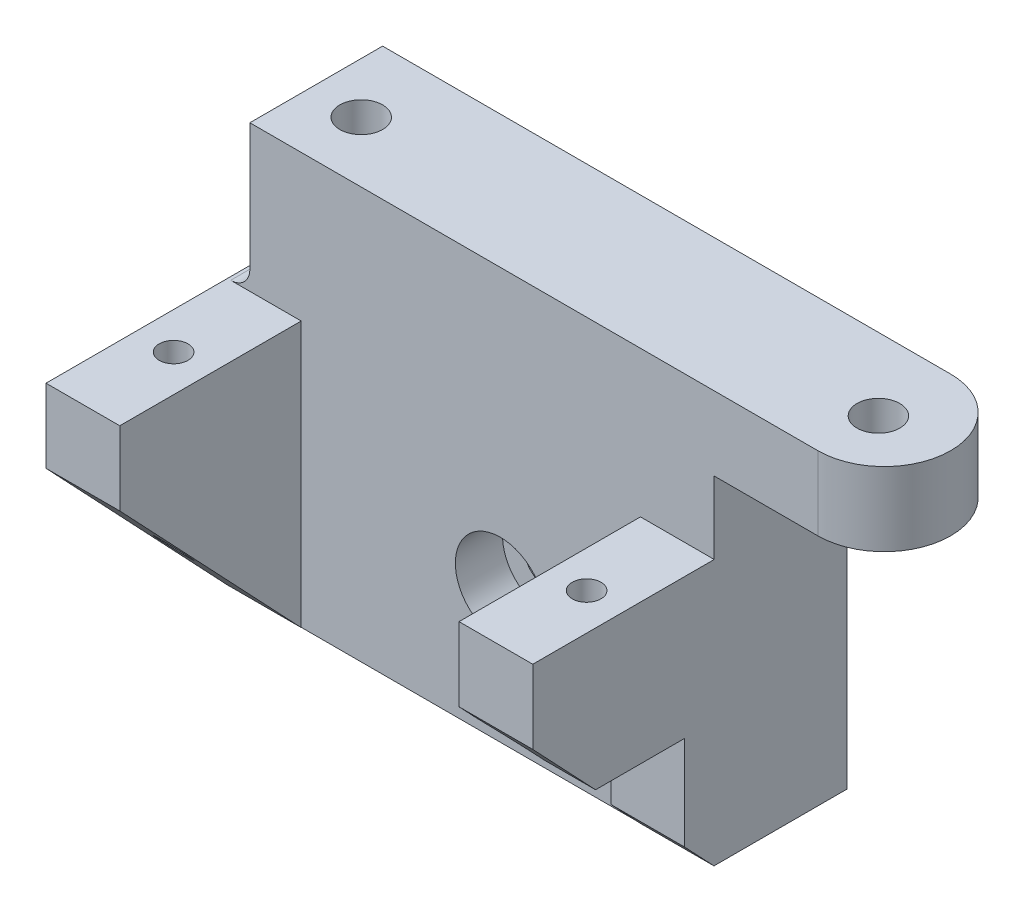
SolidWorks part; units mm, degrees
ref_plane "Front Plane" through (0, 0, 0) normal (0, 0, 1) x (1, 0, 0)
ref_plane "Top Plane" through (0, 0, 0) normal (0, 1, 0) x (1, 0, 0)
ref_plane "Right Plane" through (0, 0, 0) normal (1, 0, 0) x (0, 0, -1)
ref_plane "Model center" through (6, 0, 0) normal (1, 0, 0) x (0, 0, -1)
sketch "Sketch1" plane through (0, 0, 0) normal (0, 0, 1) x (1, 0, 0)
  line L0 (-4, 0) -> (4, 0)
  line L1 (-16.5, -8.9917) -> (16.5, -8.9917)
  line L2 (-16.5, -8.9917) -> (-16.5, 8.9917)
  line L3 (-16.5, 8.9917) -> (16.5, 8.9917)
  line L4 (16.5, -8.9917) -> (16.5, 8.9917)
  line L5 (-16.5, -8.9917) -> (16.5, 8.9917) construction
  line L6 (-16.5, 8.9917) -> (16.5, -8.9917) construction
  point P0 (0, 0)
  point P9 (0, 0)
  dimension "D1" = 8
  dimension "D2" = 33
extrude "Boss-Extrude1" add sketch "Sketch1" along normal blind 9 contours L1 L4 L3 L2 region at (-16.1242, 0, 0)
ref_plane "Plane1" through (0, 8.9917, 0) normal (0, 1, 0) x (1, 0, 0)
sketch "Sketch4" plane through (0, 8.9917, 0) normal (0, 1, 0) x (1, 0, 0)
  line L1 (0, 0) -> (0, -9) construction
  line L2 (-16.5, -9) -> (-11.5, -9)
  line L3 (-16.5, -9) -> (-16.5, -21.3)
  line L4 (-16.5, -21.3) -> (-11.5, -21.3)
  line L5 (-11.5, -9) -> (-11.5, -21.3)
  line L6 (-16.5, 0) -> (16.5, 0) construction
  line L7 (-16.5, -9) -> (16.5, -9) construction
  line L8 (11.5, -9) -> (11.5, -21.3)
  line L9 (16.5, -21.3) -> (11.5, -21.3)
  line L10 (16.5, -9) -> (16.5, -21.3)
  line L11 (16.5, -9) -> (11.5, -9)
  dimension "D1" = 5
  dimension "D2" = 12.3
extrude "Boss-Extrude2" add sketch "Sketch4" against normal blind 5
chamfer "Chamfer1" distance 12.3 distance2 13 2 edges at (-14, 3.9917, 9) (14, 3.9917, 9) first distance on face at (-14, 3.9917, 15.15) first distance on face at (14, 3.9917, 15.15)
sketch "Sketch2" plane through (0, 0, 0) normal (0, 0, -1) x (-1, 0, 0)
  line L0 (-10, 0) -> (-2, 0) construction
  circle A0 centre (-2, 0) radius 1.575
  circle A1 centre (-10, 0) radius 1.575
  point P12 (-6, 0)
  dimension "D2" = 3.15
  dimension "D1" = 8
  dimension "D3" = 6
extrude "Cut-Extrude1" cut sketch "Sketch2" against normal through all
sketch "Sketch3" plane through (0, 0, 9) normal (0, 0, 1) x (1, 0, 0)
  circle A0 centre (2, 0) radius 3.05
  circle A1 centre (10, 0) radius 3.05
  dimension "D1" = 6.1
extrude "Cut-Extrude2" cut sketch "Sketch3" against normal blind 3.2 and the other way through all
sketch "Sketch5" plane through (0, 8.9917, 0) normal (0, 1, 0) x (1, 0, 0)
  line L0 (0, 0) -> (0, -18.0516) construction
  line L1 (-16.5, 0) -> (16.5, 0) construction
  line L2 (-11.5, -15.15) -> (-16.5, -15.15) construction
  line L3 (-11.5, -21.3) -> (-11.5, -9) construction
  line L4 (-16.5, -21.3) -> (-16.5, 0) construction
  circle A0 centre (-14, -15.15) radius 0.975
  circle A1 centre (14, -15.15) radius 0.975
  dimension "D1" = 1.95
extrude "Cut-Extrude3" cut sketch "Sketch5" against normal up to surface (11.5 mm away) up to face at (-14, -2.5, 15.1579)
sketch "Sketch6" plane through (0, 8.9917, 0) normal (0, 1, 0) x (1, 0, 0)
  line L0 (-11.5, -9) -> (11.5, -9) construction
  line L1 (-16.5, -9) -> (16.5, -9)
  line L2 (-16.5, -9) -> (-16.5, 0)
  line L3 (-16.5, 0) -> (16.5, 0)
  line L4 (16.5, -9) -> (16.5, 0)
  line L5 (-16.5, -9) -> (16.5, 0) construction
  line L6 (-16.5, 0) -> (16.5, -9) construction
  point P0 (0, -4.5)
extrude "Boss-Extrude3" add sketch "Sketch6" along normal blind 9.9
sketch "Sketch7" plane through (0, 0, 9) normal (0, 0, 1) x (1, 0, 0)
  line L0 (16.5, 3.9917) -> (16.5, -8.9917) construction
  line L1 (11.5, -5.5083) -> (16.5, -5.5083)
  line L2 (11.5, -5.5083) -> (11.5, -0.5083)
  line L3 (11.5, -0.5083) -> (16.5, -0.5083)
  line L4 (16.5, -5.5083) -> (16.5, -0.5083)
  line L5 (11.5, -5.5083) -> (16.5, -0.5083) construction
  line L6 (11.5, -0.5083) -> (16.5, -5.5083) construction
  line L7 (11.5, -8.9917) -> (11.5, -2.6557) construction
  line L8 (11.5, 8.9917) -> (16.5, 8.9917) construction
  line L9 (11.5, -5.5083) -> (11.5, -10.1043)
  line L10 (11.5, -10.1043) -> (16.5, -10.1043)
  line L11 (16.5, -10.1043) -> (16.5, -5.5083)
  point P0 (14, -3.0083)
  line M4 (11.5, -8.9917) -> (11.5, -2.6557)
  dimension "D1" = 5
  dimension "D2" = 12
extrude "Cut-Extrude4" cut sketch "Sketch7" along normal blind 8 from offset 2 contours L1 L4 L3 L2 M4 | L10 L11 L1 L9 M4 region at (14, -3.0083, 9) region at (14, -7.8063, 9)
sketch "Sketch8" plane through (0, 18.8917, 0) normal (0, 1, 0) x (1, 0, 0)
  line L1 (-16.5, -9) -> (16.5, -9) construction
  line L3 (6, -55) -> (6, 55) construction
  circle A0 centre (-11.53, -4.9) radius 1.45
  dimension "D1" = 2.9
  dimension "D2" = 4.1
  dimension "D3" = 17.53
extrude "Cut-Extrude5" cut sketch "Sketch8" against normal blind 10
sketch "Sketch9" plane through (0, 18.8917, 0) normal (0, 1, 0) x (1, 0, 0)
  line L0 (-11.53, -4.5) -> (-1.4412, -4.5) construction
  line L1 (-11.53, 0) -> (-1.4412, 0)
  line L2 (-11.53, -9) -> (-1.4412, -9)
  line L3 (-16.5, -9) -> (16.5, -9) construction
  line L4 (16.5, 0) -> (-16.5, 0) construction
  arc A0 (-11.53, 0) -> (-11.53, -9) centre (-11.53, -4.5) ccw
  arc A1 (-1.4412, -9) -> (-1.4412, 0) centre (-1.4412, -4.5) ccw
  circle A2 centre (-11.53, -4.9) radius 1.45 construction
  circle A3 centre (-11.53, -4.9) radius 1.45
  point P3 (-6.4856, -4.5)
extrude "Boss-Extrude4" add sketch "Sketch9" against normal blind 5
mirror "Mirror1" about plane through (6, 0, 0) normal (1, 0, 0) of "Boss-Extrude4", "Cut-Extrude5"
sketch "Sketch10" plane through (0, 0, 0) normal (0, 0, -1) x (-1, 0, 0)
  line L0 (16.5, 8.9917) -> (11.5, 8.9917) construction
  line L1 (16.5, 18.8917) -> (14.98, 18.8917)
  line L2 (16.5, 18.8917) -> (16.5, 8.9917)
  line L3 (16.5, 8.9917) -> (14.98, 8.9917)
  line L4 (14.98, 18.8917) -> (14.98, 8.9917)
  dimension "D1" = 2
extrude "Cut-Extrude6" cut sketch "Sketch10" against normal up to surface (9 mm away) up to face at (5.4592, 6.9625, 9)
fillet "Fillet1" radius 1.3 1 edges at (-14.98, 8.9917, 4.5)
